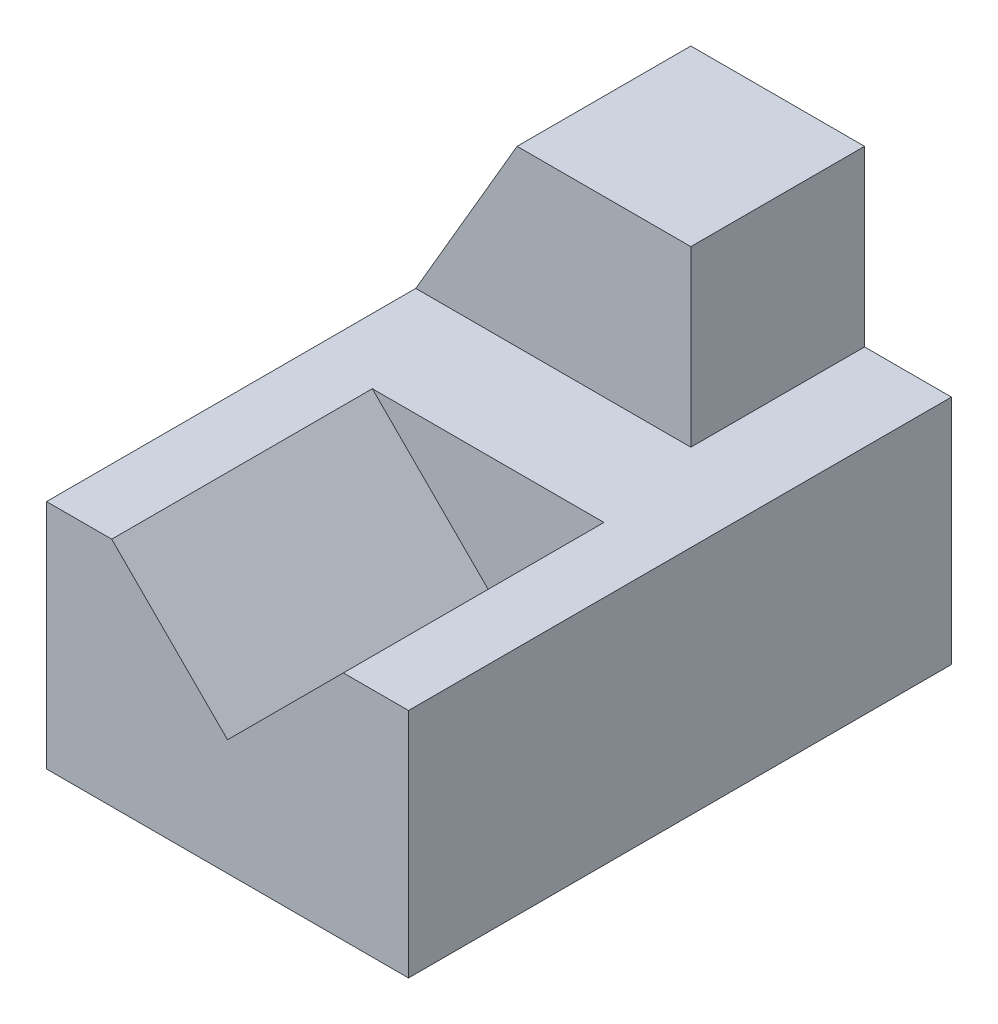
SolidWorks part; units mm, degrees
ref_plane "Front Plane" through (0, 0, 0) normal (0, 0, 1) x (1, 0, 0)
ref_plane "Top Plane" through (0, 0, 0) normal (0, 1, 0) x (1, 0, 0)
ref_plane "Right Plane" through (0, 0, 0) normal (1, 0, 0) x (0, 0, -1)
sketch "Sketch1" plane through (0, 0, 0) normal (0, 0, 1) x (1, 0, 0)
  line L0 (25, 4) -> (-25, 4)
  line L1 (-25, 28) -> (25, 28)
  line L2 (-25, 28) -> (-25, -28)
  line L3 (-25, -28) -> (25, -28)
  line L4 (25, 28) -> (25, -28)
  line L5 (-25, 28) -> (25, -28) construction
  line L6 (-25, -28) -> (25, 28) construction
  line L7 (13, 4) -> (13, 28)
  line L8 (-11, 28) -> (-25, 4)
  line L9 (-16, 4) -> (0, -12)
  line L10 (0, -12) -> (16, 4)
  point P0 (0, 0)
  dimension "D1" = 32
  dimension "D2" = 50
  dimension "D3" = 56
  dimension "D4" = 24
  dimension "D5" = 12
  dimension "D6" = 9
  dimension "D7" = 9
  dimension "D8" = 25
  dimension "D9" = 16
extrude "Boss-Extrude1" add sketch "Sketch1" along normal blind 75 contours L10 L9 L0 L2 L3 L4 region at (0, -14.0317, 0)
extrude "Boss-Extrude3" add sketch "Sketch1<4>" along normal blind 39 contours L9 L10 L0 region at (0, -1.3333, 0)
sketch "Sketch1<4>" plane through (0, 0, 0) normal (0, 0, 1) x (1, 0, 0) same geometry as "Sketch1"
extrude "Boss-Extrude4" add sketch "Sketch1<5>" along normal blind 24 contours L1 L8 L0 L7 region at (-2.7634, 15.0968, 0)
sketch "Sketch1<5>" plane through (0, 0, 0) normal (0, 0, 1) x (1, 0, 0) same geometry as "Sketch1"
